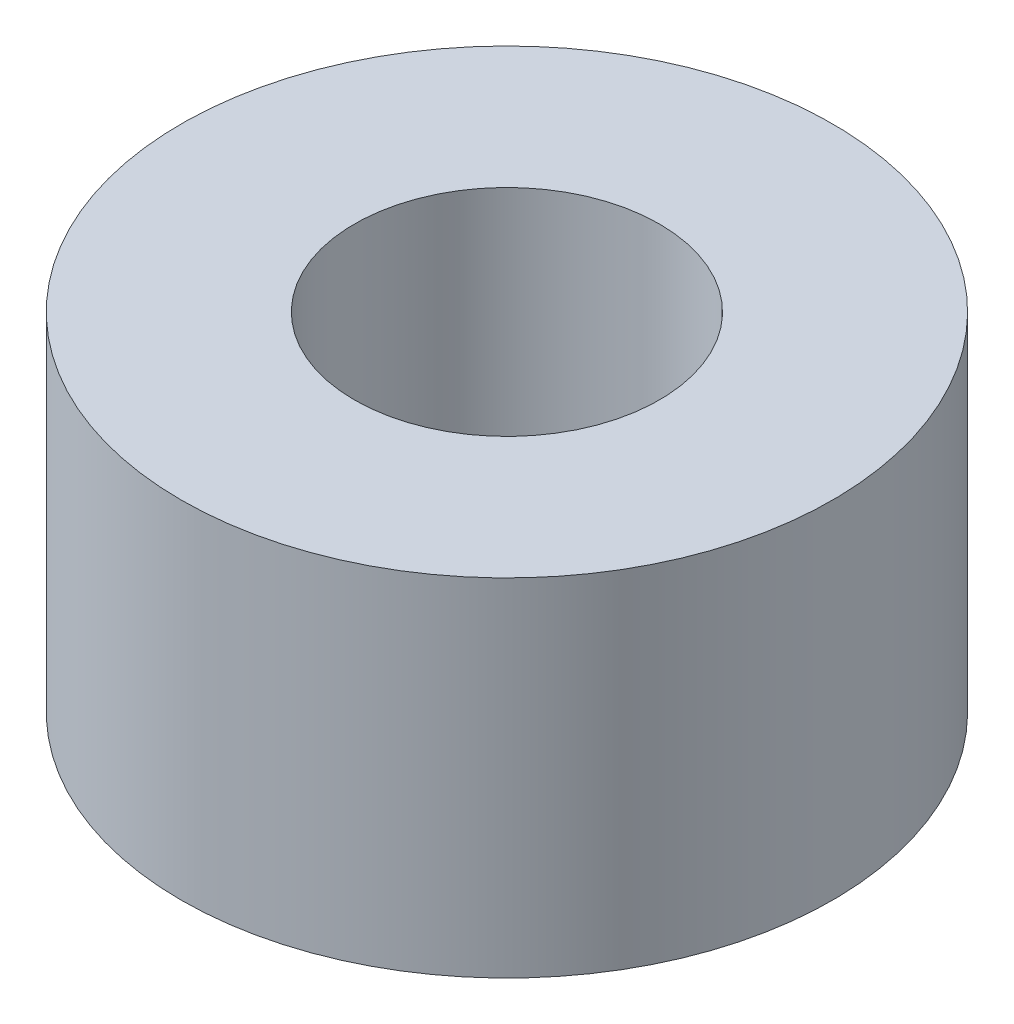
SolidWorks part; units mm, degrees
material "PET"
ref_plane "Front" through (0, 0, 0) normal (0, 0, 1) x (1, 0, 0)
ref_plane "Top" through (0, 0, 0) normal (0, 1, 0) x (1, 0, 0)
ref_plane "Right" through (0, 0, 0) normal (1, 0, 0) x (0, 0, -1)
sketch "Sketch1" plane through (0, 0, 0) normal (0, 1, 0) x (1, 0, 0)
  circle A0 centre (0, 0) radius 2.794
  circle A1 centre (0, 0) radius 5.969
  dimension "D1" = 3.175
  dimension "D2" = 5.588
extrude "Boss-Extrude1" add sketch "Sketch1" along normal blind 6.35
